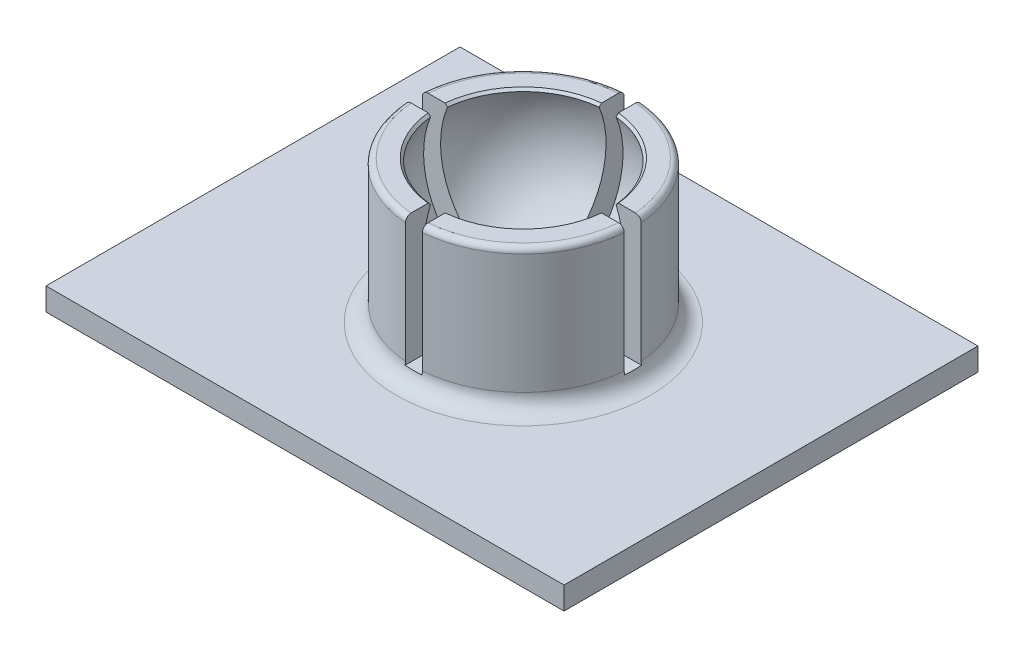
SolidWorks part; units mm, degrees
ref_plane "Front Plane" through (0, 0, 0) normal (0, 0, 1) x (1, 0, 0)
ref_plane "Top Plane" through (0, 0, 0) normal (0, 1, 0) x (1, 0, 0)
ref_plane "Right Plane" through (0, 0, 0) normal (1, 0, 0) x (0, 0, -1)
sketch "Sketch1" plane through (0, 0, 0) normal (0, 1, 0) x (1, 0, 0)
  line L0 (-23.9, 0) -> (21.9, 0) construction
  line L2 (-23.9, 18.3) -> (21.9, 18.3)
  line L3 (-23.9, 18.3) -> (-23.9, -18.3)
  line L4 (-23.9, -18.3) -> (21.9, -18.3)
  line L5 (21.9, 18.3) -> (21.9, -18.3)
  point P7 (21.9, 0)
  point P8 (-23.9, 0)
  dimension "D1" = 36.6
  dimension "D2" = 21.9
  dimension "D3" = 23.9
extrude "Boss-Extrude1" add sketch "Sketch1" along normal blind 2
sketch "Sketch2" plane through (0, 2, 0) normal (0, 1, 0) x (1, 0, 0)
  circle A0 centre (0, 0) radius 9.7
  dimension "D1" = 19.4
extrude "Boss-Extrude2" add sketch "Sketch2" along normal blind 12.5939
sketch "Sketch6" plane through (0, 0, 0) normal (0, 0, 1) x (1, 0, 0)
  line L0 (0, 0) -> (0, 19.4) construction
  line L2 (0, 19.4) -> (0, 3.2)
  line L3 (0, 3.2) -> (0, 19.4)
  arc A0 (0, 3.2) -> (0, 19.4) centre (0, 11.3) ccw
  dimension "D1" = 16.2
  dimension "D2" = 11.3
revolve "Cut-Revolve1" cut sketch "Sketch6" angle 360 about L3 region at (3.4377, 11.3, 0)
sketch "Sketch8" plane through (0, 14.5939, 0) normal (0, 1, 0) x (1, 0, 0)
  line L0 (10.7, 0.75) -> (-10.7, 0.75)
  line L1 (-0.75, 10.7) -> (0.75, 10.7)
  line L2 (-0.75, 10.7) -> (-0.75, -10.7)
  line L3 (-0.75, -10.7) -> (0.75, -10.7)
  line L4 (0.75, 10.7) -> (0.75, -10.7)
  line L5 (-0.75, 10.7) -> (0.75, -10.7) construction
  line L6 (-0.75, -10.7) -> (0.75, 10.7) construction
  line L7 (10.7, 0.75) -> (10.7, -0.75)
  line L8 (10.7, -0.75) -> (-10.7, -0.75)
  line L9 (-10.7, 0.75) -> (-10.7, -0.75)
  point P0 (0, 0)
  point P6 (0, 0)
  point P7 (0, 0)
  point P8 (0, 0)
  point P9 (9.7, -4.106)
  point P14 (0, 0)
  dimension "D1" = 1.5
  dimension "D2" = 21.4
extrude "Cut-Extrude4" cut sketch "Sketch8" against normal blind 11.3939 contours L0 L9 L8 L7 | L2 L1 L4 L3
fillet "Fillet1" radius 1.5 1 edges at (0, 2, 9.7)
chamfer "Chamfer1" distance 0.3 angle 45 4 edges at (-5.2326, 14.5939, -5.2326) (-5.2326, 14.5939, 5.2326) (5.2326, 14.5939, 5.2326) (5.2326, 14.5939, -5.2326) first distance on face at (-5.3395, 14.5939, -5.3395) first distance on face at (-5.3395, 14.5939, 5.3395) first distance on face at (5.3395, 14.5939, 5.3395) first distance on face at (5.3395, 14.5939, -5.3395)
fillet "Fillet2" radius 0.5 4 edges at (6.8589, 14.5939, 6.8589) (6.8589, 14.5939, -6.8589) (-6.8589, 14.5939, 6.8589) (-6.8589, 14.5939, -6.8589)
equation "\"board_w\"= 33.8"
equation "\"board_l\"= 41"
equation "\"stack_h\"= 19.5"
equation "\"module_w\"= 9.9"
equation "\"lens_d\"= 7.8"
equation "\"lens_from_end\"= 8"
equation "\"usb_w\"= 13"
equation "\"plug_h\"= 7"
equation "\"usb_from_back\"= 6"
equation "\"clear\"= 0.4"
equation "\"wall\"= 3"
equation "\"floor_t\"= 2.5"
equation "\"pocket_clear\"= 0.3"
equation "\"lens_clear\"= 0.6"
equation "\"plate_w\"= 16"
equation "\"plate_clear\"= 0.3"
equation "\"plate_t\"= 1.2"
equation "\"plate_seat\"= 0.8"
equation "\"window_d\"= 12"
equation "\"lid_t\"= 2"
equation "\"lid_gap\"= 1"
equation "\"groove_d\"= 1.2"
equation "\"groove_clear\"= 0.15"
equation "\"lip_top\"= 1.2"
equation "\"side_clear\"= 0.2"
equation "\"slide_clear\"= 0.2"
equation "\"ball_d\"= 16"
equation "\"ball_clear\"= 0.2"
equation "\"lip\"= 0.6"
equation "\"cup_floor\"= 1.2"
equation "\"slit_w\"= 1.5"
equation "\"slit_depth\"= \"cup_h\" - \"cup_floor\""
equation "\"lug_w\"= 16"
equation "\"m3_hole\"= 3.4"
equation "\"m3_nut\"= 5.7"
equation "\"m3_nut_d\"= 2.6"
equation "\"boss_d\"= 20"
equation "\"boss_h\"= 8"
equation "\"nut_af\"= 11.4"
equation "\"nut_t\"= 5.8"
equation "\"screw_hole\"= 6.6"
equation "\"in_l\"= \"board_l\" + 2 * \"clear\""
equation "\"in_w\"= \"board_w\" + 2 * \"clear\""
equation "\"out_l\"= \"in_l\" + 2 * \"wall\""
equation "\"out_w\"= \"in_w\" + 2 * \"wall\""
equation "\"y_groove\"= \"floor_t\" - \"plate_seat\" + \"stack_h\" + \"lid_gap\""
equation "\"groove_h\"= \"lid_t\" + 2 * \"groove_clear\""
equation "\"tray_h\"= \"y_groove\" + \"groove_h\" + \"lip_top\""
equation "\"lid_w\"= \"in_w\" + 2 * \"groove_d\" - 2 * \"side_clear\""
equation "\"lid_right\"= \"in_l\" / 2 + \"groove_d\" - \"slide_clear\""
equation "\"lid_left\"= \"out_l\" / 2"
equation "\"open_d\"= \"ball_d\" - 2 * \"lip\""
equation "\"c_ball\"= sqr( ( ( \"ball_d\" + \"ball_clear\" ) / 2 ) ^ 2 - ( \"open_d\" / 2 ) ^ 2 )"
equation "\"cup_h\"= \"cup_floor\" + ( \"ball_d\" + \"ball_clear\" ) / 2 + \"c_ball\""
equation "\"D2@Sketch1\"= \"lid_right\""
equation "\"D3@Sketch1\"=\"lid_left\""
equation "\"D1@Boss-Extrude1\"=\"lid_t\""
equation "\"D1@Sketch6\"=\"ball_d\"+\"ball_clear\""
equation "\"D2@Sketch6\"=\"lid_t\"+\"cup_h\"-\"c_ball\""
equation "\"lug_in\"= \"cup_d\" / 2 - 5"
equation "\"lug_out\"= \"cup_d\" / 2 + 4"
equation "\"finger_t\"= 1.6"
equation "\"cup_d\"= \"ball_d\" + \"ball_clear\" + 2 * \"finger_t\""
equation "\"D1@Sketch2\"=\"cup_d\""
equation "\"D1@Boss-Extrude2\"=\"cup_h\""
equation "\"D1@Sketch8\"=\"slit_w\""
equation "\"D1@Cut-Extrude4\"=\"slit_depth\""
equation "\"D1@Fillet1\"=1.5"
